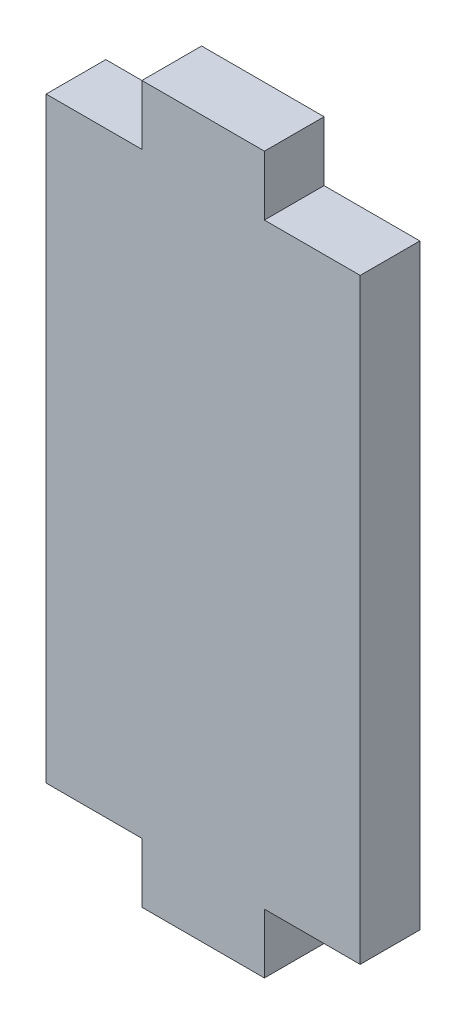
SolidWorks part; units mm, degrees
ref_plane "Front Plane" through (0, 0, 0) normal (0, 0, 1) x (1, 0, 0)
ref_plane "Top Plane" through (0, 0, 0) normal (0, 1, 0) x (1, 0, 0)
ref_plane "Right Plane" through (0, 0, 0) normal (1, 0, 0) x (0, 0, -1)
sketch "Sketch1" plane through (0, 0, 0) normal (0, 0, 1) x (1, 0, 0)
  line L1 (0, 0) -> (25.4, 0)
  line L2 (0, 0) -> (0, 57.912)
  line L3 (0, 57.912) -> (25.4, 57.912)
  line L4 (25.4, 0) -> (25.4, 57.912)
  dimension "D1" = 57.912
  dimension "D2" = 25.4
extrude "Boss-Extrude1" add sketch "Sketch1" along normal blind 4.826
sketch "Sketch2" plane through (0, 0, 4.826) normal (0, 0, 1) x (1, 0, 0)
  line L0 (25.4, 57.912) -> (0, 57.912) construction
  line L1 (7.747, 57.912) -> (17.653, 57.912)
  line L2 (7.747, 57.912) -> (7.747, 53.086)
  line L3 (7.747, 53.086) -> (17.653, 53.086)
  line L4 (17.653, 57.912) -> (17.653, 53.086)
  line L5 (12.7, 53.086) -> (12.7, 57.912) construction
  line L6 (0, 57.912) -> (0, 0) construction
  line L7 (25.4, 0) -> (25.4, 57.912) construction
  line L8 (0, 57.912) -> (7.747, 57.912)
  line L9 (0, 57.912) -> (0, 53.086)
  line L10 (0, 53.086) -> (7.747, 53.086)
  line L11 (7.747, 57.912) -> (7.747, 53.086)
  line L12 (17.653, 57.912) -> (25.4, 57.912)
  line L13 (17.653, 57.912) -> (17.653, 53.086)
  line L14 (17.653, 53.086) -> (25.4, 53.086)
  line L15 (25.4, 57.912) -> (25.4, 53.086)
  line L16 (0, 28.956) -> (25.4, 28.956) construction
  line L17 (12.7, 4.826) -> (12.7, 0) construction
  line L18 (25.4, 0) -> (25.4, 4.826)
  line L19 (17.653, 4.826) -> (25.4, 4.826)
  line L20 (17.653, 0) -> (17.653, 4.826)
  line L21 (17.653, 0) -> (25.4, 0)
  line L22 (7.747, 0) -> (7.747, 4.826)
  line L23 (0, 4.826) -> (7.747, 4.826)
  line L24 (0, 0) -> (0, 4.826)
  line L25 (0, 0) -> (7.747, 0)
  line L26 (17.653, 0) -> (17.653, 4.826)
  line L27 (7.747, 4.826) -> (17.653, 4.826)
  line L28 (7.747, 0) -> (7.747, 4.826)
  line L29 (7.747, 0) -> (17.653, 0)
  line L30 (12.7, 53.086) -> (12.7, 57.912) construction
  line M13 (0, 57.912) -> (0, 0)
  line M14 (0, 0) -> (25.4, 0)
  line M15 (25.4, 0) -> (25.4, 57.912)
  line M16 (25.4, 57.912) -> (0, 57.912)
  dimension "D1" = 9.906
  dimension "D2" = 4.826
  dimension "D3" = 12.7
extrude "Cut-Extrude1" cut sketch "Sketch2" against normal through all contours L4 L14 M15 M16 | L10 L2 M13 M16 | L20 L19 M14 M15 | L23 L22 M13 M14 region at (3.8735, 55.499, 4.826) region at (21.5265, 55.499, 4.826) region at (3.8735, 2.413, 4.826) region at (21.5265, 2.413, 4.826)
equation "\"MDF\"= 0.19in"
equation "\"PVCID\" = 2.067in"
equation "\"PVCOD\" = 2.375in"
equation "\"GenDiameter\"= 60mm"
equation "\"GenCutDiameter\" = 1.8in"
equation "\"GenCutDistance\" = 1"
equation "\"TowerHeight\" = 6in"
equation "\"TowerFrontBase\" = 3in"
equation "\"FunnelHeight\" = 1in"
equation "\"FunnelAngle\" = 20"
equation "\"TowerSideBase\" = 3in"
equation "\"TowerPanelLength\" = 2in"
equation "\"TowerPanelLeeway\" = 0.5in"
equation "\"BaseLength\" = 9in"
equation "\"BaseWidth\" = 10in"
equation "\"WheelHoleLength\" = 3.25in"
equation "\"WheelHoleWidth\" = 26mm"
equation "\"WheelHoleFromBack\" = 1in"
equation "\"DropLength\" = 1in"
equation "\"DropWidth\" = 8.5in"
equation "\"BumperWidth\" = 1in"
equation "\"SmallHexDiameter\" = 0.185in"
equation "\"SmallHexHeight\" = 0.701in"
equation "\"ScrewSize\" = 0.106in"
equation "\"BigHexDiameter\" = 0.251in"
equation "\"BigHexHeight\" = 0.374in"
equation "\"PCBThickness\" = 0.066in"
equation "\"ConnectorHeight\" = 0.517in"
equation "\"BoardHeight\" = 0.583in"
equation "\"UnoStackHeight\" = 1.351in"
equation "\"UnoStackWidth\" = 3.053in"
equation "\"UnoStackLength\" = 3.152in"
equation "\"HBridgeWidth\" = 1.797in"
equation "\"HBridgeLength\" = 2.236in"
equation "\"DSWidth\" = 1.820in"
equation "\"DSLength\" = 1.833in"
equation "\"StepperWidth\" = 1.799in"
equation "\"StepperLength\" = 2.248in"
equation "\"ULNWidth\" = 1.304in"
equation "\"ULNLength\" = 1.545in"
equation "\"VSwitchHeight\" = 0.392in"
equation "\"VSwitchWidth\" = 0.637in"
equation "\"VSwitchLength\" = 1.097in"
equation "\"SkateWheelDiameter\" = 80mm"
equation "\"SkateWheelThickness\" = 24mm"
equation "\"BaseDistance\" = 3in"
equation "\"DummyVar\" = 2in"
equation "\"D1@Sketch1\"=2*\"MDF\"+1.9in"
equation "\"D1@Boss-Extrude1\"=\"MDF\""
equation "\"D2@Sketch2\"=\"MDF\""
